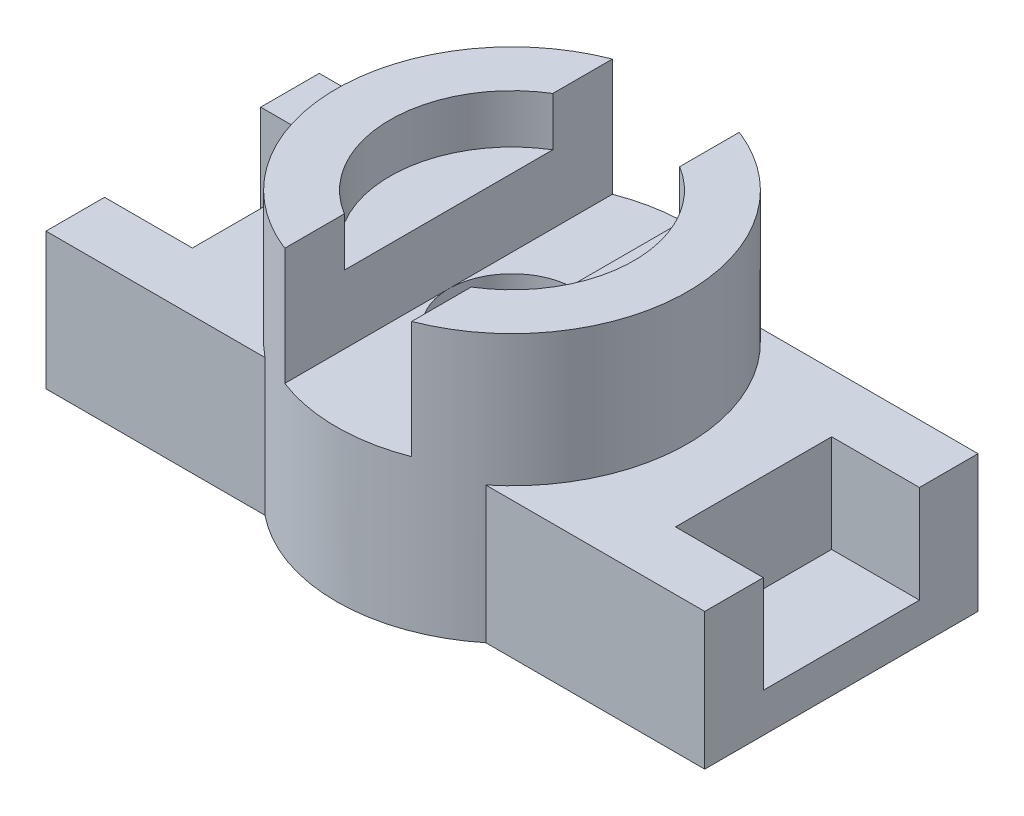
SolidWorks part; units mm, degrees
ref_plane "Front Plane" through (0, 0, 0) normal (0, 0, 1) x (1, 0, 0)
ref_plane "Top Plane" through (0, 0, 0) normal (0, 1, 0) x (1, 0, 0)
ref_plane "Right Plane" through (0, 0, 0) normal (1, 0, 0) x (0, 0, -1)
sketch "Sketch1" plane through (0, 0, 0) normal (0, 1, 0) x (1, 0, 0)
  line L0 (-67.5, -28) -> (67.5, -28)
  line L1 (-67.5, -28) -> (-67.5, 28)
  line L2 (67.5, -28) -> (67.5, 28)
  line L3 (-67.5, 28) -> (67.5, 28)
  line L4 (-67.5, -28) -> (67.5, 28) construction
  line L5 (67.5, -28) -> (-67.5, 28) construction
  circle A0 centre (0, 0) radius 36
  circle A1 centre (0, 0) radius 25
  circle A2 centre (0, 0) radius 13
  point P1 (0, 0)
  dimension "D3" = 72
  dimension "D4" = 50
  dimension "D5" = 26
  dimension "D1" = 56
  dimension "D2" = 135
extrude "Boss-Extrude1" add sketch "Sketch1" along normal blind 28 contours A0 L3 L1 L0 | A0 L0 L2 L3 region at (-49.5117, 0, 0) region at (49.5117, 0, 0)
extrude "Boss-Extrude2" add sketch "Sketch1<4>" along normal blind 55 contours A2 | A1 A2 | L0 A0 L3 A1 | L0 A0 | A0 region at (-35.0879, 0, 0) region at (0, 0, 31.2326) region at (-24.2929, 0, 0) region at (0, 0, 0)
sketch "Sketch1<4>" plane through (0, 0, 0) normal (0, 1, 0) x (1, 0, 0) same geometry as "Sketch1"
extrude "Cut-Extrude1" cut sketch "Sketch1<5>" along normal through all contours A2 region at (0, 0, 0)
sketch "Sketch1<5>" plane through (0, 0, 0) normal (0, 1, 0) x (1, 0, 0) same geometry as "Sketch1"
sketch "Sketch2" plane through (0, 55, 0) normal (0, 1, 0) x (1, 0, 0)
  line L0 (-13, -45.7531) -> (-13, 45.7531)
  line L1 (-13, -45.7531) -> (13, -45.7531)
  line L2 (-13, 45.7531) -> (13, 45.7531)
  line L3 (13, -45.7531) -> (13, 45.7531)
  line L4 (-13, -45.7531) -> (13, 45.7531) construction
  line L5 (-13, 45.7531) -> (13, -45.7531) construction
  circle A0 centre (0, 0) radius 25
  circle M6 centre (0, 0) radius 13
  circle M7 centre (0, 0) radius 36
  dimension "D1" = 50
  dimension "D2" = 26
extrude "Cut-Extrude2" cut sketch "Sketch2" against normal blind 10 contours L3 A0 | L3 A0 L0 M6 | L0 A0 L3 M6 | L0 A0 region at (-17.9149, 55, 0) region at (0, 55, 16.7495) region at (0, 55, -16.7495) region at (17.9149, 55, 0)
extrude "Cut-Extrude3" cut sketch "Sketch2<3>" against normal blind 24 contours L3 L2 L0 M7 | A0 L3 L0 M7 | L3 L2 L0 L1 region at (0, 55, -29.4842) region at (0, 55, -40.4527)
sketch "Sketch2<3>" plane through (0, 55, 0) normal (0, 1, 0) x (1, 0, 0) same geometry as "Sketch2"
sketch "Sketch3" plane through (0, 28, 0) normal (0, 1, 0) x (1, 0, 0)
  line L0 (49.5, -16) -> (49.5, 16)
  line L1 (49.5, -16) -> (85.5, -16)
  line L2 (49.5, 16) -> (85.5, 16)
  line L3 (85.5, -16) -> (85.5, 16)
  line L4 (49.5, -16) -> (85.5, 16) construction
  line L5 (49.5, 16) -> (85.5, -16) construction
  line L6 (67.5, -28) -> (67.5, 28) construction
  line L7 (0, 0) -> (0, 21.6036) construction
  line L8 (-49.5, 16) -> (-85.5, 16)
  line L9 (-85.5, -16) -> (-85.5, 16)
  line L10 (-49.5, -16) -> (-85.5, -16)
  line L11 (-49.5, -16) -> (-49.5, 16)
  point P0 (67.5, 16)
  point P1 (67.5, 0)
  point P9 (67.5, 0)
  dimension "D1" = 32
  dimension "D2" = 18
extrude "Cut-Extrude4" cut sketch "Sketch3" against normal blind 20
